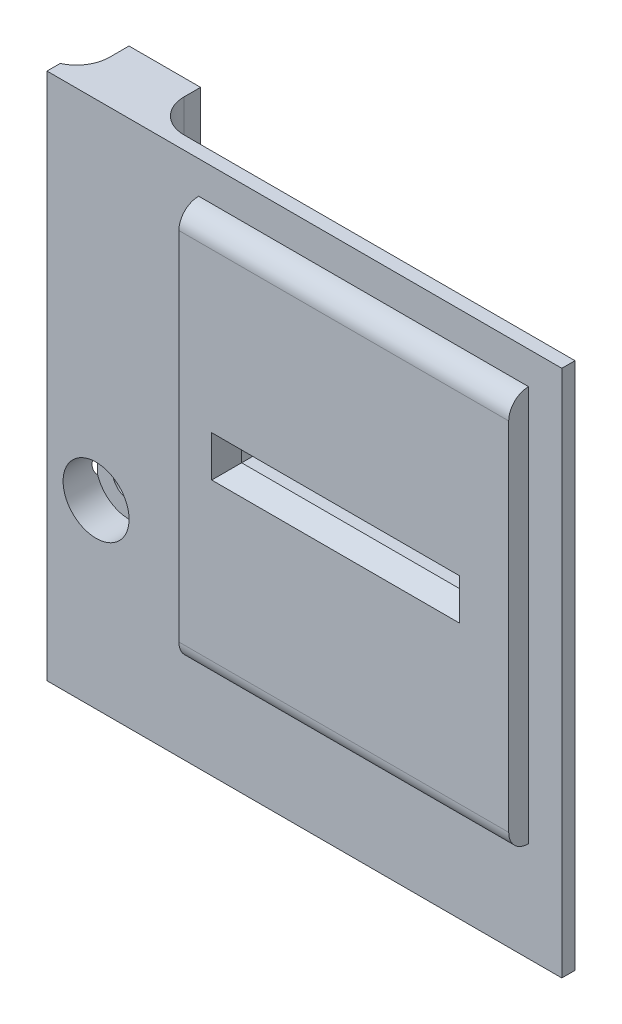
SolidWorks part; units mm, degrees
ref_plane "Front Plane" through (0, 0, 0) normal (0, 0, 1) x (1, 0, 0)
ref_plane "Top Plane" through (0, 0, 0) normal (0, 1, 0) x (1, 0, 0)
ref_plane "Right Plane" through (0, 0, 0) normal (1, 0, 0) x (0, 0, -1)
sketch "Sketch1" plane through (0, 0, 0) normal (0, 0, 1) x (1, 0, 0)
  line L1 (-65.0547, 50.908) -> (12.9453, 50.908)
  line L2 (-65.0547, 50.908) -> (-65.0547, -29.092)
  line L3 (-65.0547, -29.092) -> (12.9453, -29.092)
  line L4 (12.9453, 50.908) -> (12.9453, -29.092)
  dimension "D1" = 78
  dimension "D2" = 80
extrude "Boss-Extrude1" add sketch "Sketch1" along normal blind 2
sketch "Sketch2" plane through (0, 0, 0) normal (0, 0, -1) x (-1, 0, 0)
  line L1 (1.1147, 17.408) -> (35.5652, 17.408)
  line L2 (1.1147, 17.408) -> (1.1147, 14.2517)
  line L3 (1.1147, 14.2517) -> (35.5652, 14.2517)
  line L4 (35.5652, 17.408) -> (35.5652, 14.2517)
extrude "Cut-Extrude1" cut sketch "Sketch2" against normal blind 10
sketch "Sketch3" plane through (0, 0, 0) normal (0, 0, -1) x (-1, 0, 0)
  line L0 (-12.9453, 50.908) -> (65.0547, 50.908) construction
  line L1 (62.1274, 50.908) -> (51.2851, 50.908)
  line L2 (62.1274, 50.908) -> (62.1274, -29.092)
  line L3 (62.1274, -29.092) -> (51.2851, -29.092)
  line L4 (51.2851, 50.908) -> (51.2851, -29.092)
  line L5 (65.0547, -29.092) -> (-12.9453, -29.092) construction
extrude "Boss-Extrude2" add sketch "Sketch3" along normal blind 7.5
sketch "Sketch4" plane through (0, 0, -7.5) normal (0, 0, -1) x (-1, 0, 0)
  circle A0 centre (57.6173, -1.6836) radius 2.5
  dimension "D1" = 5
extrude "Cut-Extrude2" cut sketch "Sketch4" against normal blind 20
sketch "Sketch5" plane through (0, 0, 2) normal (0, 0, 1) x (1, 0, 0)
  circle A0 centre (-57.6173, -1.6836) radius 5
extrude "Cut-Extrude3" cut sketch "Sketch5" against normal blind 5
fillet "Fillet1" radius 5 2 edges
sketch "Sketch8" plane through (0, 0, 2) normal (0, 0, 1) x (1, 0, 0)
  line L1 (-42.0724, 45.978) -> (7.8989, 45.978)
  line L2 (-42.0724, 45.978) -> (-42.0724, -14.0104)
  line L3 (-42.0724, -14.0104) -> (7.8989, -14.0104)
  line L4 (7.8989, 45.978) -> (7.8989, -14.0104)
extrude "Boss-Extrude3" add sketch "Sketch8" along normal blind 3
fillet "Fillet3" radius 3 2 edges at (-17.0867, -14.0104, 5) (-17.0867, 45.978, 5)
sketch "Sketch9" plane through (0, 0, 2) normal (0, 0, -1) x (-1, 0, 0)
  line L0 (35.5652, 14.2517) -> (1.1147, 14.2517) construction
  line L1 (35.5652, 17.408) -> (1.1147, 17.408)
  line L2 (35.5652, 17.408) -> (35.5652, 14.2517)
  line L3 (35.5652, 14.2517) -> (1.1147, 14.2517)
  line L4 (1.1147, 17.408) -> (1.1147, 14.2517)
extrude "Cut-Extrude4" cut sketch "Sketch9" against normal blind 3 draft 27 draft outward yes
